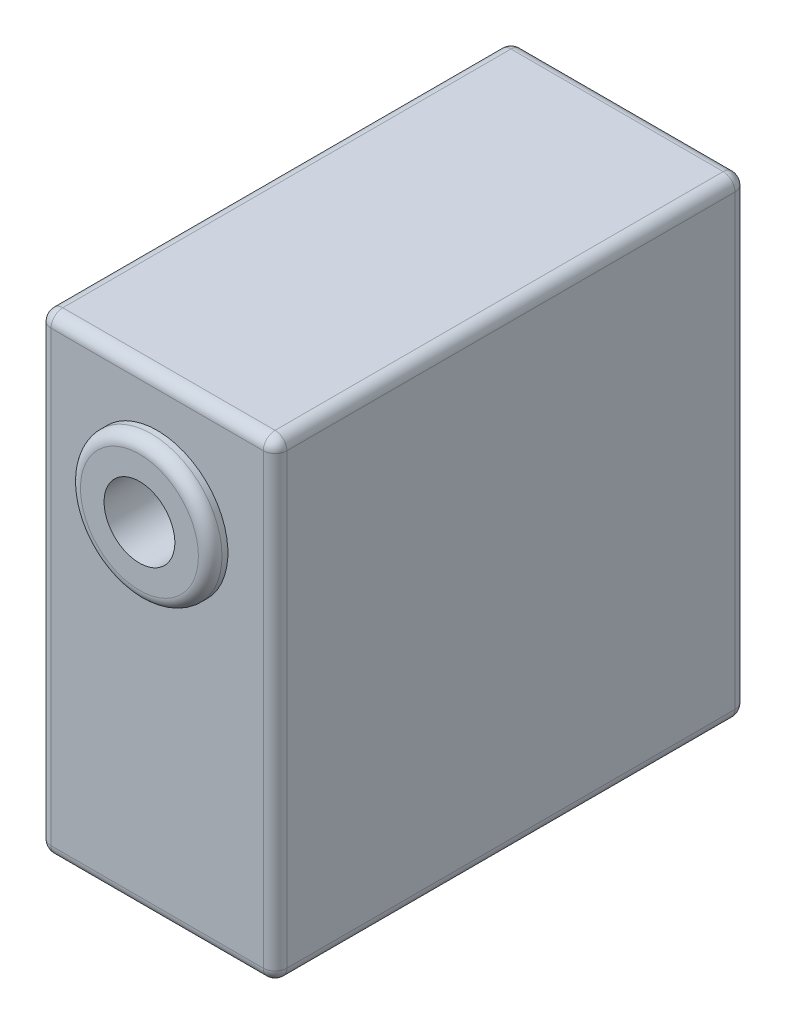
SolidWorks part; units mm, degrees
ref_plane "Front Plane" through (0, 0, 0) normal (0, 0, 1) x (1, 0, 0)
ref_plane "Top Plane" through (0, 0, 0) normal (0, 1, 0) x (1, 0, 0)
ref_plane "Right Plane" through (0, 0, 0) normal (1, 0, 0) x (0, 0, -1)
sketch "Sketch1" plane through (0, 0, 0) normal (1, 0, 0) x (0, 0, -1)
  line L0 (-13.3818, 12.8727) -> (26.6182, 12.8727)
  line L1 (26.6182, 12.8727) -> (26.6182, -27.1273)
  line L2 (26.6182, -27.1273) -> (-13.3818, -27.1273)
  line L3 (-13.3818, -27.1273) -> (-13.3818, 12.8727)
  dimension "D1" = 40
  dimension "D2" = 40
extrude "Boss-Extrude1" add sketch "Sketch1" along normal blind 20
fillet "Fillet1" radius 1 12 edges at (0, -7.1273, -26.6182) (10, -27.1273, -26.6182) (0, -27.1273, -6.6182) (10, -27.1273, 13.3818) (20, -27.1273, -6.6182) (20, -7.1273, -26.6182) (20, -7.1273, 13.3818) (0, -7.1273, 13.3818) (10, 12.8727, 13.3818) (0, 12.8727, -6.6182) (20, 12.8727, -6.6182) (10, 12.8727, -26.6182)
sketch "Sketch2" plane through (0, 0, 13.3818) normal (0, 0, 1) x (1, 0, 0)
  line L1 (1, 12.8727) -> (19, 12.8727) construction
  circle A0 centre (10, 2.8727) radius 6
  dimension "D1" = 12
  dimension "D2" = 10
extrude "Boss-Extrude2" add sketch "Sketch2" along normal blind 1.5
fillet "Fillet2" radius 1 1 edges at (16, 2.8727, 14.8818)
sketch "Sketch3" plane through (0, 0, 14.8818) normal (0, 0, 1) x (1, 0, 0)
  circle A0 centre (10, 2.8727) radius 3
  dimension "D1" = 6
sketch "Sketch4" plane through (0, 0, -26.6182) normal (0, 0, -1) x (-1, 0, 0)
  line L0 (-10, 13.403) -> (-10, -29.4763) construction
  line L1 (-19, 12.8727) -> (-1, 12.8727) construction
  circle A0 centre (-10, 2.8727) radius 6
  dimension "D1" = 12
  dimension "D2" = 10
extrude "Boss-Extrude4" add sketch "Sketch4" along normal blind 0.9
fillet "Fillet3" radius 1 1 edges at (4, 2.8727, -27.5182)
extrude "Cut-Extrude2" cut sketch "Sketch3" along normal through all and the other way through all
